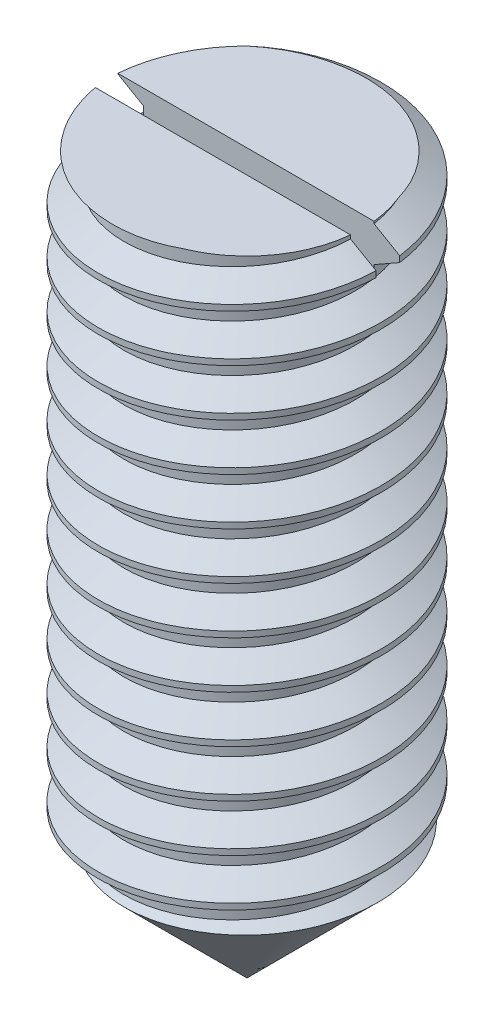
SolidWorks part; units mm, degrees
material "Gray Cast Iron"
ref_plane "Front Plane" through (0, 0, 0) normal (0, 0, 1) x (1, 0, 0)
ref_plane "Top Plane" through (0, 0, 0) normal (0, 1, 0) x (1, 0, 0)
ref_plane "Right Plane" through (0, 0, 0) normal (1, 0, 0) x (0, 0, -1)
sketch "Sketch1" plane through (0, 0, 0) normal (0, 0, 1) x (1, 0, 0)
  line L0 (0, 0) -> (0, 15) construction
  line L1 (0, 0) -> (-3, 3)
  line L2 (-3, 3) -> (-3, 15)
  line L3 (-3, 15) -> (0, 15)
  line L4 (0, 0) -> (0, 15)
  dimension "D1" = 15
  dimension "D2" = 6
  dimension "D3" = 45
revolve "Revolve1" add sketch "Sketch1" angle 360 about L0
thread "Thread1" pitch 1 method cut profile "Thread Profile1" start angle 0, offset 5, length 40, pitch 1, diameter 6
ref_plane "Plane1" through (-3, 20, 0) normal (0, 0, 1) x (-1, 0, 0)
sketch "Thread Profile1" plane through (-3, 20, 0) normal (0, 0, 1) x (-1, 0, 0)
  line L0 (0, 0) -> (0, 1) construction
  line L11 (0, 0) -> (0, 0.875)
  line L12 (0, 0.875) -> (-0.5413, 0.5625)
  line L13 (-0.5413, 0.5625) -> (-0.5413, 0.3125)
  line L15 (-0.5413, 0.3125) -> (0, 0)
  line L17 (-0.5413, 0.4375) -> (0, 0.4375) construction
  point P2 (0, 0)
  dimension "Pitch" = 1
  dimension "Profile_Angle" = 60
  dimension "Profile_Land" = 0.25
  dimension "Profile_Height" = 0.5413
sketch "Sketch5" plane through (0, 15, 0) normal (0, 1, 0) x (1, 0, 0)
  line L1 (-3.986, -0.25) -> (3.986, -0.25)
  line L2 (-3.986, -0.25) -> (-3.986, 0.25)
  line L3 (-3.986, 0.25) -> (3.986, 0.25)
  line L4 (3.986, -0.25) -> (3.986, 0.25)
  line L5 (-3.986, -0.25) -> (3.986, 0.25) construction
  line L6 (-3.986, 0.25) -> (3.986, -0.25) construction
  point P0 (0, 0)
  dimension "D1" = 0.5
extrude "Cut-Extrude1" cut sketch "Sketch5" against normal blind 1 and the other way through all
